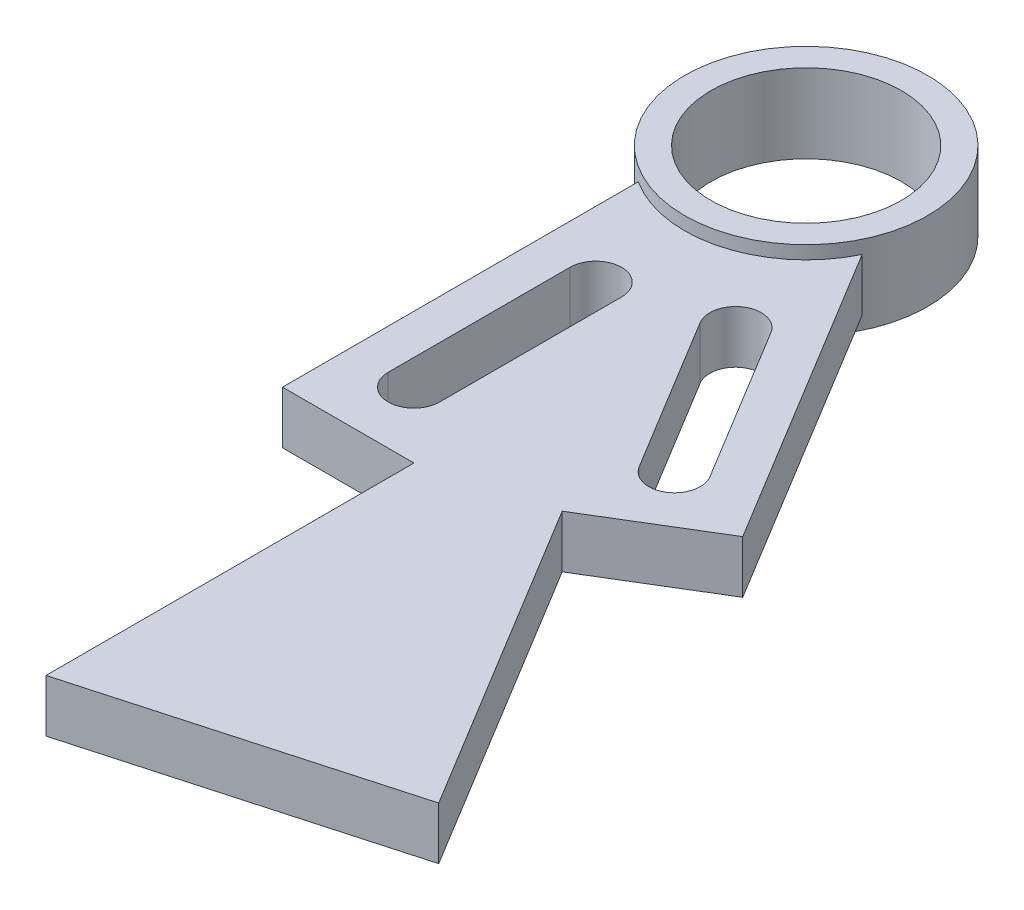
SolidWorks part; units mm, degrees
material "AISI 4130 Steel, annealed at 865C"
ref_plane "Front Plane" through (0, 0, 0) normal (0, 0, 1) x (1, 0, 0)
ref_plane "Top Plane" through (0, 0, 0) normal (0, 1, 0) x (1, 0, 0)
ref_plane "Right Plane" through (0, 0, 0) normal (1, 0, 0) x (0, 0, -1)
sketch "Sketch1" plane through (0, 0, 0) normal (0, 1, 0) x (1, 0, 0)
  line L0 (0, -50.4952) -> (0, -14.6812) construction
  line L1 (26.2122, -43.1589) -> (7.621, -12.5482) construction
  line L2 (0, -47.3837) -> (0, -25.4127) construction
  line L5 (-3.1115, -47.3837) -> (-3.1115, -25.4127)
  line L8 (-7.9375, -55.3212) -> (7.9375, -55.3212)
  line L9 (21.9331, -51.4041) -> (35.5016, -43.1633)
  line L10 (-7.9375, -55.3212) -> (-7.9375, -12.3505)
  line L11 (35.5016, -43.1633) -> (13.1954, -6.4357)
  line L12 (7.9375, -55.3212) -> (7.9375, -99.7712)
  line L13 (21.9331, -51.4041) -> (45.0072, -89.396)
  line L14 (7.9375, -99.7712) -> (45.0072, -89.396)
  line L15 (0, -14.6812) -> (0, 0) construction
  line L16 (0, -55.3212) -> (0, -50.4952) construction
  line L17 (28.7173, -47.2837) -> (26.2122, -43.1589)
  line L18 (3.1115, -47.3837) -> (3.1115, -25.4127)
  line L19 (13.1918, -21.7205) -> (24.597, -40.4994) construction
  line L20 (15.8512, -20.1054) -> (27.2564, -38.8842)
  line L21 (10.5323, -23.3357) -> (21.9375, -42.1146)
  line L22 (7.621, -12.5482) -> (0, 0) construction
  line L23 (0, 0) -> (20.5378, -73.3801) construction
  line L25 (184.7645, -304.2186) -> (14.7218, -24.2397) construction
  line L27 (0, 0) -> (26.4723, -94.5836) construction
  circle A0 centre (0, 0) radius 11.5062
  circle A1 centre (0, 0) radius 14.6812
  arc A2 (-3.1115, -47.3837) -> (3.1115, -47.3837) centre (0, -47.3837) ccw
  arc A3 (3.1115, -25.4127) -> (-3.1115, -25.4127) centre (0, -25.4127) ccw
  arc A4 (15.8512, -20.1054) -> (10.5323, -23.3357) centre (13.1918, -21.7205) ccw
  arc A5 (21.9375, -42.1146) -> (27.2564, -38.8842) centre (24.597, -40.4994) ccw
  point P9 (0, -36.3982)
  point P14 (18.8944, -31.11)
  point P23 (0, -55.3212)
  point P26 (28.7173, -47.2837)
  point P33 (0, -50.4952)
  point P36 (26.2122, -43.1589)
  point P38 (0, -22.3012)
  dimension "D2" = 29.3624
  dimension "D3" = 40.64
  dimension "D4" = 4.826
  dimension "D6" = 44.45
  dimension "D7" = 7.9375
  dimension "D5" = 4.826
  dimension "D8" = 7.62
  dimension "D9" = 76.2
extrude "Bearing extrude" add sketch "Sketch1" along normal mid plane 9.525 contours A1 A0 region at (-6.8368, 0, -12.521)
extrude "Boss-Extrude2" add sketch "Sketch1<5>" along normal mid plane 6.35 contours A1 L10 L8 L12 L14 L13 L9 L11 A4 A2 region at (15.7016, 0, 56.1007)
sketch "Sketch1<5>" plane through (0, 0, 0) normal (0, 1, 0) x (1, 0, 0) same geometry as "Sketch1"
sketch3d "Tab Point"
  line L0 (20.5378, 0, 73.3801) -> (20.5378, 22.225, 73.3801) construction
  line L1 (0, 0, 0) -> (20.5378, 0, 73.3801) construction
  line L2 (0, 0, 0) -> (26.4723, 0, 94.5836) construction
  dimension "D1" = 22.225
equation "\"Apex_thickness\"= .25"
equation "\"Bearing_diameter\"= .906"
equation "\"A-arm_angle\"= 32.91"
equation "\"D1@Sketch1\"=\"Bearing_diameter\""
equation "\"D1@Boss-Extrude2\"= \"Apex_thickness\""
equation "\"apex slot\"= 1.4"
equation "\"tube diameter\"= 5 / 8"
